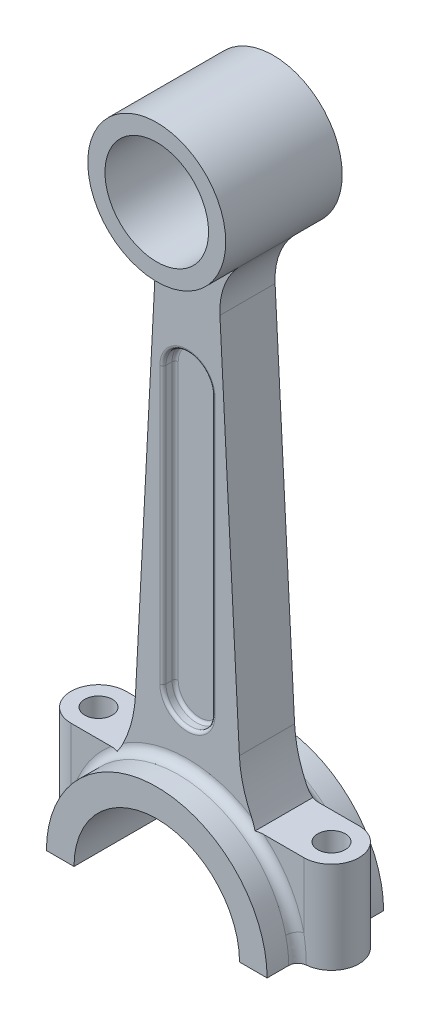
SolidWorks part; units mm, degrees
ref_plane "Front Plane" through (0, 0, 0) normal (0, 0, 1) x (1, 0, 0)
ref_plane "Top Plane" through (0, 0, 0) normal (0, 1, 0) x (1, 0, 0)
ref_plane "Right Plane" through (0, 0, 0) normal (1, 0, 0) x (0, 0, -1)
sketch "Sketch1" plane through (0, 0, 0) normal (0, 0, 1) x (1, 0, 0)
  line L0 (0, 57.2834) -> (0, -143.9166) construction
  line L1 (-58.3268, -1.4123) -> (73.2969, -1.4123) construction
  line L2 (-10, 37.1278) -> (-17.8497, -112.6534)
  line L3 (10, 37.1278) -> (17.8497, -112.6534)
  line L4 (-27, -143.9166) -> (-36, -143.9166)
  line L5 (27, -143.9166) -> (36, -143.9166)
  circle A0 centre (0, 57.2834) radius 22.5
  circle A1 centre (0, 57.2834) radius 16.9
  arc A2 (27, -143.9166) -> (-27, -143.9166) centre (0, -143.9166) ccw
  arc A3 (36, -143.9166) -> (-36, -143.9166) centre (0, -143.9166) ccw
  point P7 (0, 0)
  point P8 (0, 0)
  dimension "D1" = 45
  dimension "D2" = 33.8
  dimension "D3" = 201.2
  dimension "D4" = 54
  dimension "D5" = 20
  dimension "D6" = 72
  dimension "D7" = 6
extrude "Boss-Extrude2" add sketch "Sketch1" along normal mid plane 38 contours A0 A1 | A2 L4 A3 L5 region at (-11.5231, 75.8639, 0)
extrude "Boss-Extrude3" add sketch "Sketch1<4>" along normal mid plane 18 contours A3 L3 A0 L2 region at (0, -43.5621, 0)
sketch "Sketch1<4>" plane through (0, 0, 0) normal (0, 0, 1) x (1, 0, 0) same geometry as "Sketch1"
sketch "Sketch11" plane through (0, 0, 9) normal (0, 0, 1) x (1, 0, 0)
  line L0 (0, 57.2834) -> (0, -143.9166) construction
  line L1 (0, -88.3166) -> (0, 1.6834) construction
  line L2 (-8, -88.3166) -> (-8, 1.6834)
  line L3 (8, -88.3166) -> (8, 1.6834)
  arc A0 (-8, -88.3166) -> (8, -88.3166) centre (0, -88.3166) ccw
  arc A1 (8, 1.6834) -> (-8, 1.6834) centre (0, 1.6834) ccw
  point P6 (0, -43.3166)
  dimension "D2" = 8
  dimension "D1" = 90
extrude "Cut-Extrude4" cut sketch "Sketch11" against normal blind 4
mirror "Mirror3" about plane through (0, 0, 0) normal (0, 0, 1) of "Cut-Extrude4"
fillet "Fillet4" radius 1 16 edges at (0, 9.6834, 5) (0, 9.6834, 9) (0, -96.3166, 5) (0, -96.3166, 9) (8, -43.3166, 5) (8, -43.3166, 9) (-8, -43.3166, 5) (-8, -43.3166, 9) (0, -96.3166, -5) (0, -96.3166, -9) (8, -43.3166, -5) (8, -43.3166, -9) (-8, -43.3166, -5) (-8, -43.3166, -9) (0, 9.6834, -5) (0, 9.6834, -9)
combine bodies "Combine2" operation type add bodies to combine 116 108
fillet "Fillet3" radius 40 2 edges at (17.8497, -112.6534, 0) (-17.8497, -112.6534, 0)
ref_plane "Plane1" through (0, -113.9166, 0) normal (0, -1, 0) x (-1, 0, 0)
sketch "Sketch4" plane through (0, -113.9166, 0) normal (0, -1, 0) x (-1, 0, 0)
  line L0 (-38, 0) -> (43.9063, 0) construction
  line L1 (38, 0) -> (-38, 0) construction
  line L2 (38, -9) -> (-38, -9)
  line L3 (38, 9) -> (-38, 9)
  arc A0 (38, -9) -> (38, 9) centre (38, 0) ccw
  arc A1 (-38, 9) -> (-38, -9) centre (-38, 0) ccw
  point P4 (0, 0)
  dimension "D2" = 9
  dimension "D1" = 76
extrude "Boss-Extrude4" add sketch "Sketch4" along normal up to surface (30 mm away) up to face at (31.5, -143.9166, 0)
sketch "Sketch9" plane through (0, 0, -9) normal (0, 0, -1) x (-1, 0, 0)
  line L1 (-27, -143.9166) -> (27, -143.9166)
  line L4 (-27, -143.9166) -> (27, -143.9166)
  arc A1 (27, -143.9166) -> (-27, -143.9166) centre (0, -143.9166) ccw
  arc A4 (27, -143.9166) -> (-27, -143.9166) centre (0, -143.9166) ccw
  dimension "D1" = 0
extrude "Cut-Extrude2" cut sketch "Sketch9" against normal through all
sketch "Sketch10" plane through (0, -143.9166, 0) normal (0, -1, 0) x (1, 0, 0)
  circle A0 centre (-38, 0) radius 4.5
  circle A1 centre (38, 0) radius 4.5
extrude "Cut-Extrude3" cut sketch "Sketch10" against normal through all
fillet "Fillet2" radius 22.5 2 edges at (-10, 37.1278, 0) (10, 37.1278, 0)
fillet "Fillet5" radius 3 2 edges at (0, -107.9166, -9) (0, -107.9166, 9)
